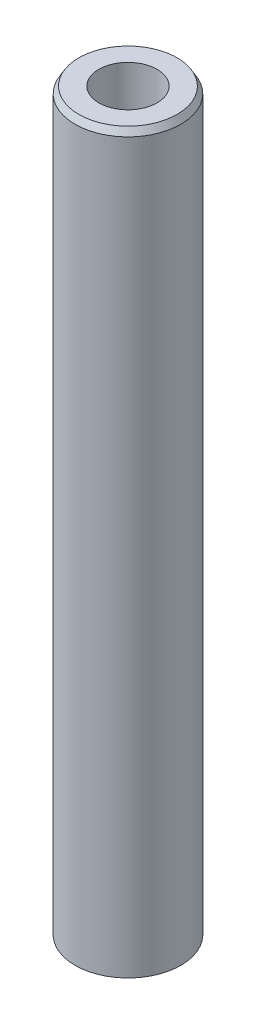
SolidWorks part; units mm, degrees
ref_plane "Front Plane" through (0, 0, 0) normal (0, 0, 1) x (1, 0, 0)
ref_plane "Top Plane" through (0, 0, 0) normal (0, 1, 0) x (1, 0, 0)
ref_plane "Right Plane" through (0, 0, 0) normal (1, 0, 0) x (0, 0, -1)
sketch "Sketch1" plane through (0, 0, 0) normal (0, 1, 0) x (1, 0, 0)
  circle A0 centre (0, 0) radius 20
  dimension "SHAFT_OD" = 40
extrude "Boss-Extrude1" add sketch "Sketch1" along normal blind 279.2428
sketch "Sketch2" plane through (0, 0, 0) normal (0, 1, 0) x (1, 0, 0)
  circle A0 centre (0, 0) radius 10.9991
  dimension "BORE_D" = 21.9983
extrude "Cut-Extrude1" cut sketch "Sketch2" along normal through all
chamfer "Chamfer1" distance 2.4931 angle 30 2 edges at (0, 279.2428, 20) (0, 0, 20) first distance on face at (0, 279.2428, 20) first distance on face at (0, 0, 10.9991)
